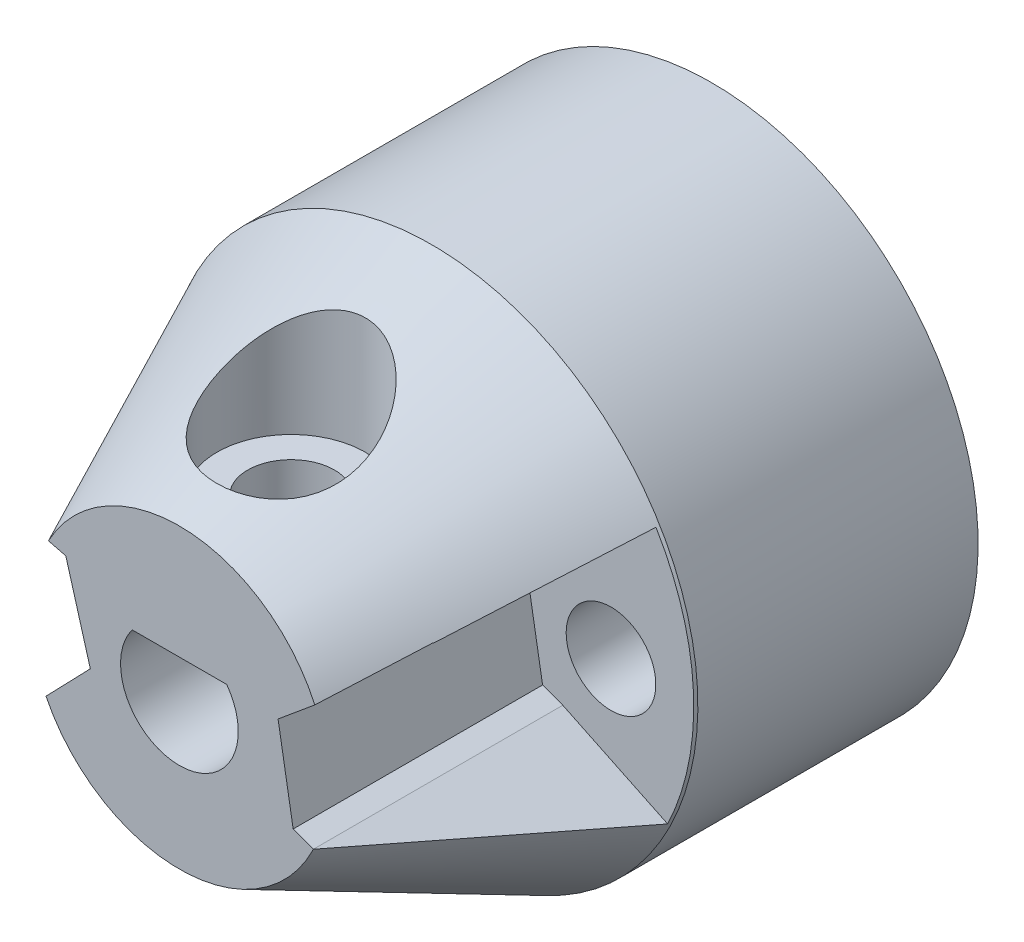
SolidWorks part; units mm, degrees
ref_plane "Plano frontal" through (0, 0, 0) normal (0, 0, 1) x (1, 0, 0)
ref_plane "Plano superior" through (0, 0, 0) normal (0, 1, 0) x (1, 0, 0)
ref_plane "Plano direito" through (0, 0, 0) normal (1, 0, 0) x (0, 0, -1)
sketch "Esboço2" plane through (0, 0, 10) normal (0, 0, 1) x (1, 0, 0)
  circle A0 centre (0, 0) radius 9.5
extrude "Ressalto-extrusão3" add sketch "Esboço2" along normal blind 9 draft 25
sketch "Esboço8" plane through (0, 0, 19) normal (0, 0, 1) x (1, 0, 0)
  line L0 (0, -2.1) -> (0, 1.25) construction
  line L1 (-1.6875, 1.25) -> (1.6875, 1.25)
  circle A0 centre (0, 0) radius 2.1
extrude "Corte-extrusão1" cut sketch "Esboço8" against normal blind 8 contours A0 L0 L1 | L0 A0 L1 region at (-0.9314, -0.2704, 19) region at (0.9314, -0.2704, 19)
ref_plane "Plano2" through (0, 9.25, 0) normal (0, -1, 0) x (-1, 0, 0)
sketch "Esboço12" plane through (0, 9.25, 0) normal (0, -1, 0) x (-1, 0, 0)
  circle A0 centre (0.0138, -14.9994) radius 1.55
extrude "Corte-extrusão4" cut sketch "Esboço12" against normal blind 8 and the other way blind 10 contours A0
sketch "Esboço20" plane through (0, 9.25, 0) normal (0, -1, 0) x (-1, 0, 0)
  circle A0 centre (0.0138, -14.9994) radius 2.65
extrude "Corte-extrusão5" cut sketch "Esboço20" against normal blind 8 and the other way blind 5
ref_plane "Plano3" through (0, 17.25, 0) normal (0, -1, 0) x (-1, 0, 0)
sketch "Esboço24" plane through (0, 17.25, 0) normal (0, -1, 0) x (-1, 0, 0)
  circle A0 centre (0.0138, -14.9994) radius 1.55
curve "Hélice/Espiral1" pitch 0.2 height 17 turns 85
ref_plane "Plano4" through (0, 0, 20) normal (0, 0, -1) x (-1, 0, 0)
sketch "Esboço25" plane through (0, 0, 20) normal (0, 0, -1) x (-1, 0, 0)
  line L1 (7.1348, 3.1214) -> (4.0537, 2.353)
  line L2 (4.0537, 2.353) -> (3.1786, -0.6995)
  line L3 (3.1786, -0.6995) -> (5.3846, -2.9836)
  line L4 (5.3846, -2.9836) -> (8.4656, -2.2152)
  line L5 (8.4656, -2.2152) -> (9.3407, 0.8373)
  line L6 (9.3407, 0.8373) -> (7.1348, 3.1214)
  line L7 (-5.9612, 3.1294) -> (-8.9407, 2.0313)
  line L8 (-8.9407, 2.0313) -> (-9.4795, -1.098)
  line L9 (-9.4795, -1.098) -> (-7.0388, -3.1294)
  line L10 (-7.0388, -3.1294) -> (-4.0593, -2.0313)
  line L11 (-4.0593, -2.0313) -> (-3.5205, 1.098)
  line L12 (-3.5205, 1.098) -> (-5.9612, 3.1294)
  circle A4 centre (6.2597, 0.0689) radius 2.75 construction
  circle A5 centre (-6.5, 0) radius 2.75 construction
  point P1 (0, 0)
extrude "Corte-extrusão6" cut sketch "Esboço25" against normal blind 10 and the other way blind 9.8
sketch "Esboço36" plane through (0, 0, 10) normal (0, 0, -1) x (-1, 0, 0)
  line L0 (-0.9998, 0.98) -> (0.9998, 0.98)
  circle A0 centre (-6.5, 0) radius 1.6
  circle A1 centre (6.5, 0) radius 1.6
  circle A2 centre (0, 0) radius 1.4
  circle A3 centre (0, 0) radius 4
  circle M1 centre (0, 0) radius 9.5
extrude "Corte-extrusão8" cut sketch "Esboço36" against normal blind 10 contours A0 | A1 region at (6.5, 0, 10) region at (-6.5, 0, 10)
extrude "Ressalto-extrusão4" add sketch "Esboço36<3>" along normal blind 10 contours A3 A1 A0 M1 | L0 A2 region at (0, -0.1194, 10) region at (9.2313, 0, 10)
sketch "Esboço36<3>" plane through (0, 0, 10) normal (0, 0, -1) x (-1, 0, 0) same geometry as "Esboço36"
sketch "Esboço46" plane through (0, 0, 19) normal (0, 0, 1) x (1, 0, 0)
  line L0 (0, 1.25) -> (0, 5.3032) construction
  line L1 (-1.6875, 1.25) -> (1.6875, 1.25) construction
  arc A0 (4.8306, 2.1885) -> (-4.673, 2.5074) centre (0, 0) ccw construction
ref_plane "Plano8" through (0, 0, 0) normal (1, 0, 0) x (0, 0, -1)
sketch "Esboço49" plane through (0, 0, 20) normal (0, 0, -1) x (-1, 0, 0)
  line L0 (4.673, 2.5074) -> (8.3711, 4.4917)
  line L1 (4.7604, -2.3373) -> (7.8189, -5.3958)
  line L2 (-4.8306, 2.1885) -> (-8.1415, 4.8955)
  line L3 (-4.78, -2.2969) -> (-8.5627, -4.1146)
  line L6 (-3.5205, 1.098) -> (-4.0593, -2.0313)
  line L7 (-4.8306, 2.1885) -> (-3.5205, 1.098)
  line L8 (4.0537, 2.353) -> (4.673, 2.5074)
  line L9 (3.1786, -0.6995) -> (4.0537, 2.353)
  line L10 (4.7604, -2.3373) -> (3.1786, -0.6995)
  line L11 (-4.0593, -2.0313) -> (-4.78, -2.2969)
  line L12 (-3.5205, 1.098) -> (-4.0593, -2.0313)
  line L13 (-4.8306, 2.1885) -> (-3.5205, 1.098)
  line L14 (4.0537, 2.353) -> (4.673, 2.5074)
  line L15 (3.1786, -0.6995) -> (4.0537, 2.353)
  line L16 (4.7604, -2.3373) -> (3.1786, -0.6995)
  line L17 (-4.0593, -2.0313) -> (-4.78, -2.2969)
  circle A1 centre (0, 0) radius 9.5
  arc A2 (4.673, 2.5074) -> (-4.8306, 2.1885) centre (0, 0) ccw
  arc A3 (-4.78, -2.2969) -> (4.7604, -2.3373) centre (0, 0) ccw
  arc A4 (4.673, 2.5074) -> (-4.8306, 2.1885) centre (0, 0) ccw
  arc A5 (-4.78, -2.2969) -> (4.7604, -2.3373) centre (0, 0) ccw
  circle A6 centre (0, 0) radius 9.5
  dimension "D1" = 0
  dimension "D2" = 0
extrude "Corte-extrusão10" cut sketch "Esboço49" against normal blind 9.9 and the other way blind 10 contours L1 A6 L0 L14 L15 L16 region at (-6.8045, -0.1835, 20)
extrude "Corte-extrusão11" cut sketch "Esboço49<4>" against normal blind 9.9 and the other way blind 9.9 contours L2 A6 L3 L17 L12 L13 region at (6.9025, 0.1718, 20)
sketch "Esboço49<4>" plane through (0, 0, 20) normal (0, 0, -1) x (-1, 0, 0) same geometry as "Esboço49"
